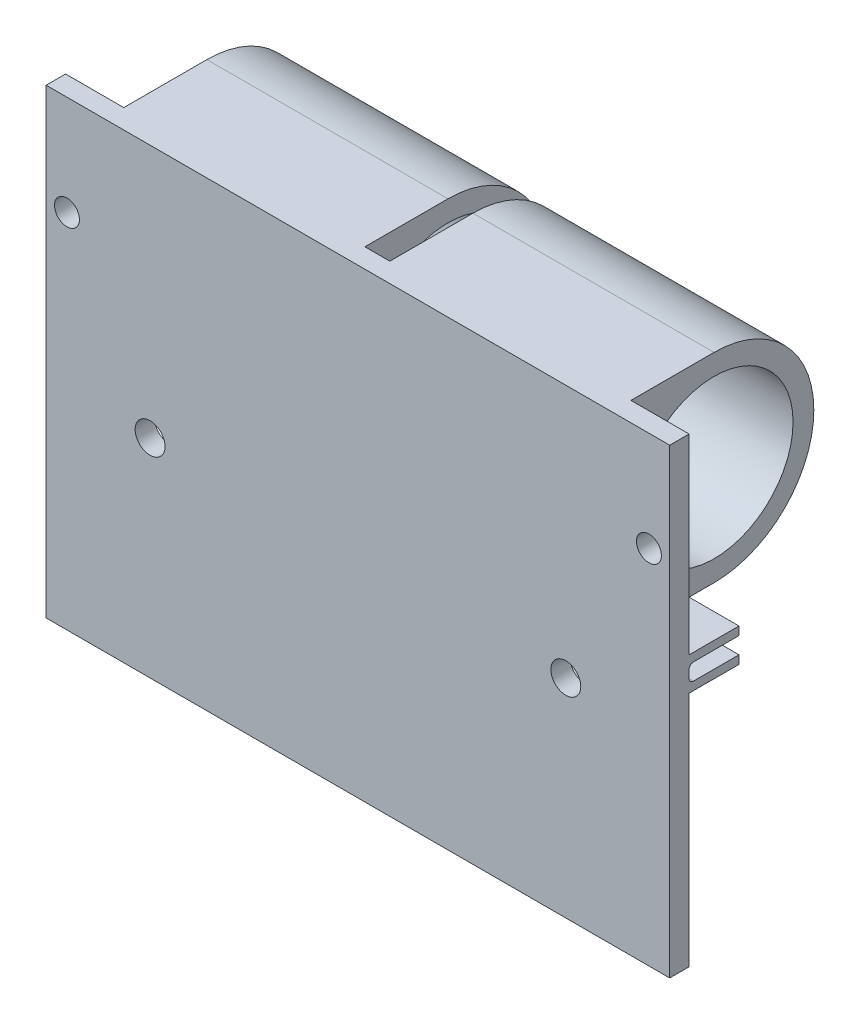
SolidWorks part; units mm, degrees
material "1060 Alloy"
ref_plane "Front Plane" through (0, 0, 0) normal (0, 0, 1) x (1, 0, 0)
ref_plane "Top Plane" through (0, 0, 0) normal (0, 1, 0) x (1, 0, 0)
ref_plane "Right Plane" through (0, 0, 0) normal (1, 0, 0) x (0, 0, -1)
sketch "Sketch1" plane through (0, 0, 0) normal (0, 0, 1) x (1, 0, 0)
  line L0 (-37.5, 0) -> (-25, 0) construction
  line L1 (37.5, -10.5) -> (30, -10.5)
  line L2 (37.5, -10.5) -> (37.5, 10.5)
  line L3 (37.5, 10.5) -> (-37.5, 10.5)
  line L4 (-37.5, -10.5) -> (-37.5, 10.5)
  line L5 (37.5, -10.5) -> (-37.5, 10.5) construction
  line L6 (37.5, 10.5) -> (-37.5, -10.5) construction
  line L7 (-30, -10.5) -> (-37.5, -10.5)
  line L8 (-25, 0) -> (-12.5, 0) construction
  line L9 (-12.5, 0) -> (0, 0) construction
  line L10 (0, 0) -> (12.5, 0) construction
  line L11 (12.5, 0) -> (25, 0) construction
  line L12 (25, 0) -> (37.5, 0) construction
  line L13 (-5, -10.5) -> (-20, -10.5)
  line L14 (20, -10.5) -> (5, -10.5)
  line L15 (-35, 10.5) -> (-35, 8) construction
  line L16 (-35, 8) -> (-37.5, 8) construction
  line L17 (-25, -10.5) -> (-25, 10.5) construction
  line L18 (-12.5, -10.5) -> (-12.5, 10.5) construction
  line L19 (12.5, -10.5) -> (12.5, 10.5) construction
  arc A0 (-20, -10.5) -> (-30, -10.5) centre (-25, -10.5) cw
  arc A1 (5, -10.5) -> (-5, -10.5) centre (0, -10.5) cw
  arc A2 (30, -10.5) -> (20, -10.5) centre (25, -10.5) cw
  circle A3 centre (-25, -10.5) radius 1.7999
  circle A4 centre (0, -10.5) radius 1.7999
  circle A5 centre (25, -10.5) radius 1.7999
  circle A6 centre (-35, 8) radius 1.5
  circle A7 centre (-15, 8) radius 1.5
  circle A8 centre (-10, 8) radius 1.5
  circle A9 centre (10, 8) radius 1.5
  circle A10 centre (35, 8) radius 1.5
  circle A11 centre (15, 8) radius 1.5
  point P0 (0, 0)
  dimension "D4" = 5
  dimension "D5" = 3.5999
  dimension "D7" = 3
  dimension "D1" = 75
  dimension "D2" = 21
  dimension "D3" = 12.5
  dimension "D6" = 2.5
extrude "Boss-Extrude1" add sketch "Sketch1" along normal blind 7
ref_plane "Plane1" through (0, 2.25, 0) normal (0, 1, 0) x (1, 0, 0)
sketch "Sketch2" plane through (0, 2.25, 0) normal (0, 1, 0) x (1, 0, 0)
  line L1 (-37.5, -13.55) -> (-12.5, -13.55) construction
  line L7 (37.5, -7) -> (-37.5, -7)
  line L8 (37.5, -7) -> (37.5, -20.1)
  line L11 (37.5, -20.1) -> (-37.5, -20.1)
  line L12 (-37.5, -7) -> (-37.5, -20.1)
  line L13 (37.5, -7) -> (-37.5, -20.1) construction
  line L14 (37.5, -20.1) -> (-37.5, -7) construction
  line L15 (-12.5, -13.55) -> (12.5, -13.55) construction
  line L16 (12.5, -13.55) -> (37.5, -13.55) construction
  line L17 (12.5, -13.55) -> (12.5, -7) construction
  line L18 (-12.5, -13.55) -> (-12.5, -7) construction
  circle A0 centre (0, -13.55) radius 2.5
  circle A1 centre (6.0001, -13.55) radius 2.6999
  circle A2 centre (-6.0001, -13.55) radius 2.6999
  circle A3 centre (6.0001, -13.55) radius 1.3498
  circle A4 centre (-6.0001, -13.55) radius 1.3498
  circle A5 centre (-18.9999, -13.55) radius 1.3498
  circle A6 centre (-18.9999, -13.55) radius 2.6999
  circle A7 centre (-25, -13.55) radius 2.5
  circle A8 centre (-31.0001, -13.55) radius 1.3498
  circle A9 centre (-31.0001, -13.55) radius 2.6999
  circle A10 centre (31.0001, -13.55) radius 1.3498
  circle A11 centre (31.0001, -13.55) radius 2.6999
  circle A12 centre (25, -13.55) radius 2.5
  circle A13 centre (18.9999, -13.55) radius 1.3498
  circle A14 centre (18.9999, -13.55) radius 2.6999
  point P4 (0, -13.55)
  dimension "D2" = 5
  dimension "D3" = 5.3999
  dimension "D6" = 2.6997
  dimension "D1" = 13.1
  dimension "D4" = 6.0001
  dimension "D5" = 6.0001
  dimension "D7" = 25
extrude "Boss-Extrude2" add sketch "Sketch2" against normal blind 6.988 contours L7 L12 L11 L8 A11 A9 A7 A2 A1 A0 A6 A12 A14 | A9 A8 | A6 A5 | A2 A4 | A1 A3 | A14 A13 | A11 A10 region at (36.7386, 2.25, 13.55) region at (3.3766, 2.25, 13.55) region at (-8.6237, 2.25, 13.55) region at (-21.6234, 2.25, 13.55) region at (-33.6237, 2.25, 13.55) region at (28.3766, 2.25, 13.55) region at (16.3763, 2.25, 13.55)
extrude "Cut-Extrude1" cut sketch "Sketch2<3>" against normal blind 2.5 contours A9 A8 | A6 A5 | A2 A4 | A1 A3 | A14 A13 | A11 A10 region at (3.3766, 2.25, 13.55) region at (-8.6237, 2.25, 13.55) region at (-21.6234, 2.25, 13.55) region at (-33.6237, 2.25, 13.55) region at (28.3766, 2.25, 13.55) region at (16.3763, 2.25, 13.55)
sketch "Sketch2<3>" plane through (0, 2.25, 0) normal (0, 1, 0) x (1, 0, 0) same geometry as "Sketch2"
ref_plane "Plane2" through (-37.5, -4.738, 7) normal (-1, 0, 0) x (0, 0, 1)
sketch "Sketch5" plane through (0, 2.25, 0) normal (0, 1, 0) x (1, 0, 0)
  line L1 (-37.5, -7) -> (37.5, -7)
  line L2 (-37.5, -7) -> (-37.5, -20.1)
  line L3 (-37.5, -20.1) -> (37.5, -20.1)
  line L4 (37.5, -7) -> (37.5, -20.1)
  line L5 (-37.5, -7) -> (37.5, -20.1) construction
  line L6 (-37.5, -20.1) -> (37.5, -7) construction
  point P4 (0, -13.55)
extrude "Cut-Extrude3" cut sketch "Sketch5" against normal blind 21.082
sketch "Sketch6" plane through (0, 10.5, 0) normal (0, 1, 0) x (1, 0, 0)
  line L4 (37.5, 0) -> (-37.5, 0)
  line L5 (-37.5, 0) -> (-37.5, -7)
  line L6 (-37.5, -7) -> (37.5, -7)
  line L7 (37.5, -7) -> (37.5, 0)
  line L8 (37.5, 0) -> (-37.5, 0)
  line L9 (-37.5, 0) -> (-37.5, -7)
  line L10 (-37.5, -7) -> (37.5, -7)
  line L11 (37.5, -7) -> (37.5, 0)
  dimension "D1" = 0
extrude "Boss-Extrude3" add sketch "Sketch6" along normal blind 9.5
sketch "Sketch8" plane through (0, 0, 0) normal (0, 0, -1) x (-1, 0, 0)
  line L6 (-37.5, 20) -> (37.5, 20)
  line L8 (-37.5, 20) -> (-37.5, -18.0302)
  line L9 (-37.5, -18.0302) -> (37.5, -18.0302)
  line L10 (37.5, 20) -> (37.5, -18.0302)
  line L11 (-37.5, 20) -> (37.5, -18.0302) construction
  line L12 (-37.5, -18.0302) -> (37.5, 20) construction
  point P4 (0, 0.9849)
extrude "Cut-Extrude4" cut sketch "Sketch8" against normal blind 4.666
ref_plane "Plane4" through (0, -35.5, 0) normal (0, -1, 0) x (-1, 0, 0)
sketch "Sketch10" plane through (0, -35.5, 0) normal (0, -1, 0) x (-1, 0, 0)
  line L1 (-37.5, -7) -> (37.5, -7)
  line L2 (-37.5, -7) -> (-37.5, -4.666)
  line L3 (-37.5, -4.666) -> (37.5, -4.666)
  line L4 (37.5, -7) -> (37.5, -4.666)
  line L5 (-37.5, -7) -> (37.5, -4.666) construction
  line L6 (-37.5, -4.666) -> (37.5, -7) construction
  point P4 (0, -5.833)
extrude "Boss-Extrude5" add sketch "Sketch10" against normal up to surface (25 mm away) up to face at (12.5, -10.5, 5.833)
sketch "Sketch11" plane through (0, 0, 4.666) normal (0, 0, -1) x (-1, 0, 0)
  circle A0 centre (-25, -10.5) radius 1.7999
  circle A1 centre (0, -10.5) radius 1.7999
  circle A2 centre (25, -10.5) radius 1.7999
extrude "Cut-Extrude5" cut sketch "Sketch11" against normal blind 5
sketch "Sketch15" plane through (0, 0, 7) normal (0, 0, 1) x (1, 0, 0)
  line L1 (-20.5223, 1.9953) -> (24.1312, 1.9953)
  line L2 (-20.5223, 1.9953) -> (-20.5223, 15.6126)
  line L3 (-20.5223, 15.6126) -> (24.1312, 15.6126)
  line L4 (24.1312, 1.9953) -> (24.1312, 15.6126)
  line L5 (-20.5223, 1.9953) -> (24.1312, 15.6126) construction
  line L6 (-20.5223, 15.6126) -> (24.1312, 1.9953) construction
  line L7 (-7.3653, -8.2939) -> (4.3629, -8.2939)
  line L8 (-7.3653, -8.2939) -> (-7.3653, -14.2814)
  line L9 (-7.3653, -14.2814) -> (4.3629, -14.2814)
  line L10 (4.3629, -8.2939) -> (4.3629, -14.2814)
  line L11 (-7.3653, -8.2939) -> (4.3629, -14.2814) construction
  line L12 (-7.3653, -14.2814) -> (4.3629, -8.2939) construction
  point P4 (1.8044, 8.8039)
  point P9 (-1.5012, -11.2877)
extrude "Boss-Extrude7" add sketch "Sketch15" against normal up to surface (2.334 mm away) up to face at (23.2001, -10.5, 4.666)
ref_plane "Plane5" through (30.5, 0, 0) normal (1, 0, 0) x (0, 0, -1)
sketch "Sketch16" plane through (30.5, 0, 0) normal (1, 0, 0) x (0, 0, -1)
  line L0 (-4.666, 6.5) -> (-4.666, 9.5) construction
  line L1 (-4.666, 6.5) -> (-4.666, 9.5)
  line L2 (-4.666, 20) -> (-4.666, -35.5) construction
  line L3 (5.334, 20) -> (-4.666, 20)
  line L4 (5.334, -4) -> (-4.666, -4)
  line L5 (-4.666, 20) -> (-4.666, -4)
  circle A0 centre (5.334, 8) radius 9.5
  arc A1 (5.334, -4) -> (5.334, 20) centre (5.334, 8) ccw
  circle A3 centre (5.334, 8) radius 12 construction
  point P5 (-4.666, 8)
  point P13 (16.834, 8)
  dimension "D1" = 19
  dimension "D3" = 10
  dimension "D2" = 2.5
extrude "Boss-Extrude9" add sketch "Sketch16" against normal blind 29 separate body contours L4 A1 L3 L5 L1 A0 region at (30.5, 8, 4.3404)
mirror "Mirror1" about plane through (0, 0, 0) normal (1, 0, 0) of bodies 114
combine bodies "Combine1" operation type add bodies to combine 115 114 113
sketch "Sketch17" plane through (0, 0, 0) normal (1, 0, 0) x (0, 0, -1)
  line L0 (-4.666, -35.5) -> (-7, -35.5) construction
  line L1 (5.334, -35.5) -> (-4.666, -35.5)
  line L3 (5.334, -11.5) -> (-4.666, -11.5)
  line L4 (-4.666, 20) -> (-4.666, -35.5) construction
  line L5 (-4.666, -11.5) -> (-4.666, -35.5)
  circle A2 centre (5.334, 8) radius 9.5 construction
  circle A3 centre (5.334, 8) radius 9.5 construction
  circle A5 centre (5.334, -23.5) radius 9.5
  arc A6 (5.334, -35.5) -> (5.334, -11.5) centre (5.334, -23.5) ccw
  circle A8 centre (5.334, -23.5) radius 12 construction
  point P2 (16.8097, -12.4915)
  point P3 (5.334, -16)
  point P13 (16.8097, -19.9915)
  dimension "D1" = 19
  dimension "D2" = 2.5
extrude "Boss-Extrude11" add sketch "Sketch17" along normal mid plane 29
sketch "Sketch18" plane through (0, 0, 4.666) normal (0, 0, -1) x (-1, 0, 0)
  line L0 (-14.5, -11.5) -> (-14.5, -35.5) construction
  line L1 (-14.5, -14) -> (-14.5, -33) construction
  line L2 (-14.5, -11.5) -> (-14.5, -35.5)
  line L3 (-14.5, -14) -> (-14.5, -33)
  line L4 (-30.5, 20) -> (-30.5, -4) construction
  line L5 (-30.5, 20) -> (-30.5, -4)
  line L6 (-30.5, -4) -> (-37.5, -4)
  line L7 (-37.5, 20) -> (-37.5, -35.5) construction
  line L8 (-37.5, -4) -> (-37.5, -6)
  line L9 (-37.5, -6) -> (-21.77, -6)
  line L10 (-1.5, -4) -> (-30.5, -4) construction
  line L11 (-21.77, -6) -> (-21.77, -7.0074)
  line L12 (-37.5, -7) -> (-22.77, -7)
  line L13 (-22.77, -7) -> (-22.77, -7.0074)
  line L14 (-18.7626, -4) -> (-16.114, -4)
  line L15 (-37.5, -3) -> (-30.5, -3)
  line L16 (-37.5, -3) -> (-37.5, -4)
  circle A1 centre (-18.7626, -7.0074) radius 1.5
  arc A2 (-18.7626, -4) -> (-21.77, -7.0074) centre (-18.7626, -7.0074) cw
  arc A3 (-16.114, -4) -> (-22.77, -7.0074) centre (-18.7626, -7.0074) cw
  arc A5 (-18.7626, -3) -> (-22.77, -7.0074) centre (-18.7626, -7.0074) cw construction
  line M15 (-1.5, -4) -> (-30.5, -4)
  line M16 (-30.5, -4) -> (-30.5, 20)
  line M18 (-37.5, 20) -> (-37.5, -35.5)
  dimension "D2" = 3
  dimension "D3" = 1
  dimension "D1" = 2
  dimension "D4" = 1
extrude "Boss-Extrude12" add sketch "Sketch18" along normal blind 6 separate body contours L15 L6 M18 M16 | A3 A2 L11 L9 L12 L13 M15 M18 | A1 region at (34, -3.5, 4.666) region at (17.4383, -4.238, 4.666) region at (18.7626, -7.0074, 4.666)
mirror "Mirror2" about plane through (0, 0, 0) normal (1, 0, 0) of bodies 121 119 120
combine bodies "Combine2" operation type add bodies to combine 122 124 120 119 121 118 123
fillet "Fillet2" radius 0.508 15 edges at (-28.1313, -4, 4.666) (21.77, -6.5037, 4.666) (-21.77, -6.5037, 4.666) (-22.77, -7.0037, 4.666) (22.77, -7.0037, 4.666) (29.635, -6, 4.666) (-29.635, -6, 4.666) (16.636, -9.134, 4.666) (-16.636, -9.134, 4.666) (-17.2626, -7.0074, -1.334) (-17.2626, -7.0074, 4.666) (17.2626, -7.0074, -1.334) (17.2626, -7.0074, 4.666) (-17.1125, -10.6594, 4.666) (17.1125, -10.6594, 4.666)
